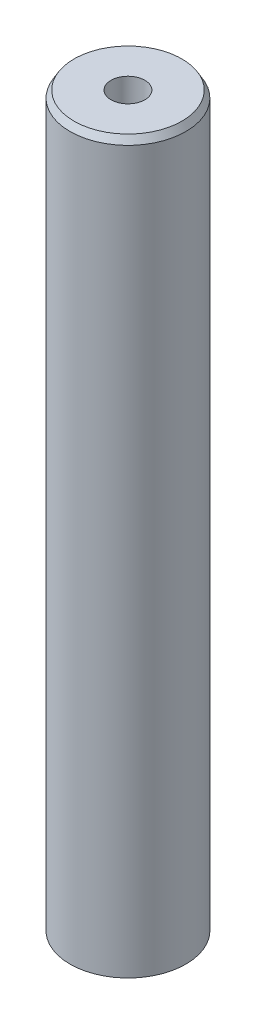
SolidWorks part; units mm, degrees
ref_plane "Front Plane" through (0, 0, 0) normal (0, 0, 1) x (1, 0, 0)
ref_plane "Top Plane" through (0, 0, 0) normal (0, 1, 0) x (1, 0, 0)
ref_plane "Right Plane" through (0, 0, 0) normal (1, 0, 0) x (0, 0, -1)
sketch "Sketch1" plane through (0, 0, 0) normal (0, 1, 0) x (1, 0, 0)
  circle A0 centre (0, 0) radius 47.5
  dimension "SHAFT_OD" = 95
extrude "Boss-Extrude1" add sketch "Sketch1" along normal blind 600
sketch "Sketch2" plane through (0, 0, 0) normal (0, 1, 0) x (1, 0, 0)
  circle A0 centre (0, 0) radius 13.8771
  dimension "BORE_D" = 27.7541
extrude "Cut-Extrude1" cut sketch "Sketch2" along normal through all
chamfer "Chamfer1" distance 5.6924 angle 30 2 edges at (0, 600, 47.5) (0, 0, 47.5) first distance on face at (0, 600, 47.5) first distance on face at (0, 0, 13.8771)
